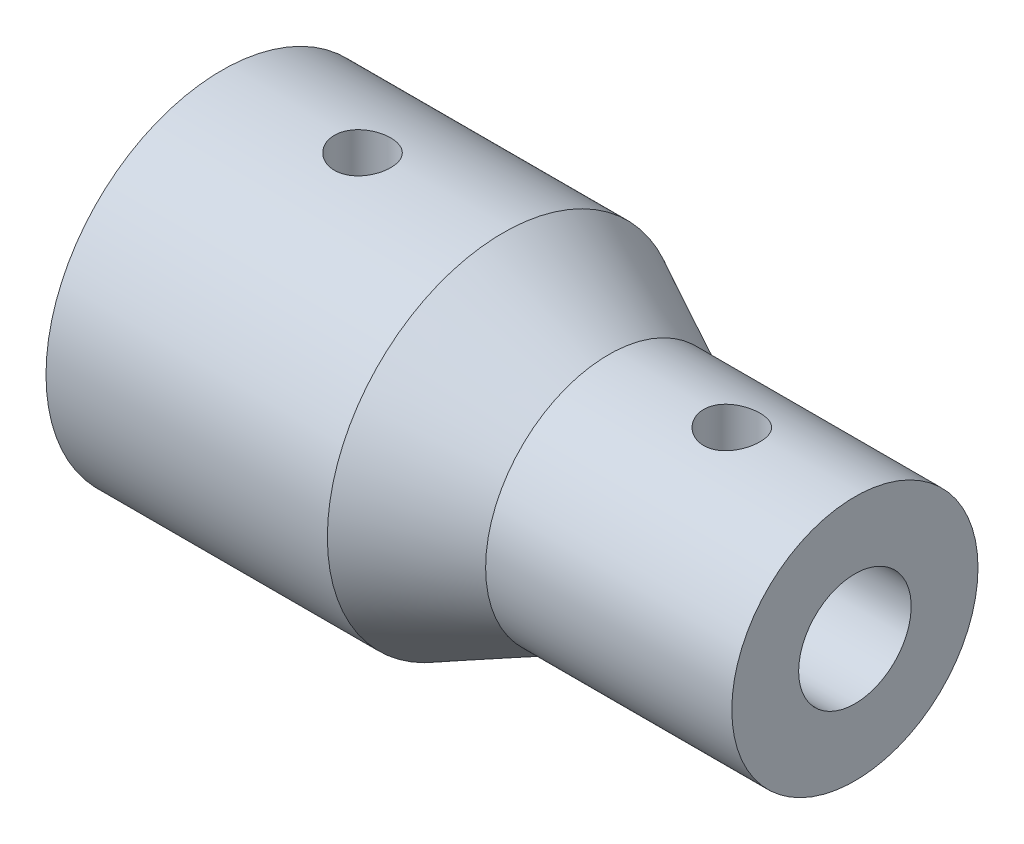
SolidWorks part; units mm, degrees
ref_plane "Front Plane" through (0, 0, 0) normal (0, 0, 1) x (1, 0, 0)
ref_plane "Top Plane" through (0, 0, 0) normal (0, 1, 0) x (1, 0, 0)
ref_plane "Right Plane" through (0, 0, 0) normal (1, 0, 0) x (0, 0, -1)
sketch "Sketch1" plane through (0, 0, 0) normal (0, 1, 0) x (1, 0, 0)
  line L0 (0, 0) -> (50114.9151, 0) construction
  line L1 (0, -1002.2983) -> (0, 0) construction
  line L2 (-10.16, 3.3655) -> (0, 3.3655)
  line L3 (0, 6.35) -> (3.81, 4.445)
  line L4 (-10.16, 3.3655) -> (-10.16, 6.35)
  line L5 (-10.16, 6.35) -> (0, 6.35)
  line L8 (12.7, 4.445) -> (12.7, 2.032)
  line L9 (0, 3.3655) -> (0, 50114.9151) construction
  line L10 (0, 3.3655) -> (2.54, 2.032)
  line L11 (2.54, 2.032) -> (12.7, 2.032)
  line L12 (3.81, 4.445) -> (12.7, 4.445)
  line L13 (0.4092, 3.3655) -> (50000.4092, 3.3655) construction
  line L14 (0, 6.35) -> (50000, 6.35) construction
  point P10 (2.3097, 2.032)
  dimension "D1" = 4.064
  dimension "D2" = 6.731
  dimension "D3" = 2.54
  dimension "D4" = 12.7
  dimension "D5" = 8.89
  dimension "D6" = 22.86
  dimension "D7" = 10.16
  dimension "D8" = 3.81
revolve "Revolve1" add sketch "Sketch1" angle 360 about L0
sketch "Sketch2" plane through (0, 0, 0) normal (0, 1, 0) x (1, 0, 0)
  line L0 (0, 0) -> (50000, 0) construction
  line L1 (0, 6.35) -> (-10.16, 6.35) construction
  line L2 (-5.08, 6.35) -> (-5.08, 0) construction
  line L3 (8.255, 4.445) -> (8.255, 0) construction
  line L4 (12.7, 4.445) -> (3.81, 4.445) construction
  circle A0 centre (-5.08, 0) radius 1.016
  circle A1 centre (8.255, 0) radius 1.016
  dimension "D1" = 2.032
  dimension "D2" = 2.032
extrude "Cut-Extrude1" cut sketch "Sketch2" along normal through all
pattern_circular "CirPattern1" count 2 every 90 about axis through (-10.16, 0, 0) along (-1, 0, 0) of "Cut-Extrude1"
equation "\"D2@Sketch2\"=\"D1@Sketch2\""
